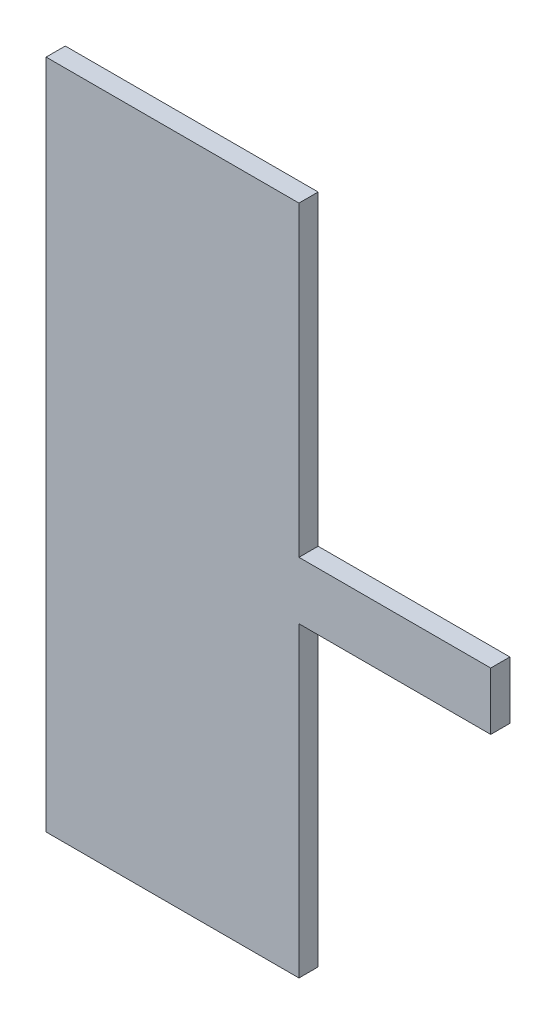
SolidWorks part; units mm, degrees
ref_plane "Front Plane" through (0, 0, 0) normal (0, 0, 1) x (1, 0, 0)
ref_plane "Top Plane" through (0, 0, 0) normal (0, 1, 0) x (1, 0, 0)
ref_plane "Right Plane" through (0, 0, 0) normal (1, 0, 0) x (0, 0, -1)
sketch "Sketch1" plane through (0, 0, 0) normal (0, 0, 1) x (1, 0, 0)
  line L3 (15.5494, 25) -> (29.7363, 25) construction
  line L6 (29.7363, -10) -> (16.5494, -10)
  line L7 (29.7363, 6) -> (39.7363, 6)
  line L8 (39.7363, 6) -> (39.7363, 9)
  line L9 (39.7363, 9) -> (29.7363, 9)
  line L10 (29.7363, -10) -> (29.7363, 6)
  line L11 (29.7363, 9) -> (29.7363, 25)
  line L12 (16.5494, -10) -> (16.5494, 25)
  line L13 (16.5494, 25) -> (29.7363, 25)
  dimension "D1" = 3
  dimension "D2" = 16
  dimension "D3" = 10
extrude "Boss-Extrude1" add sketch "Sketch1" along normal blind 1
